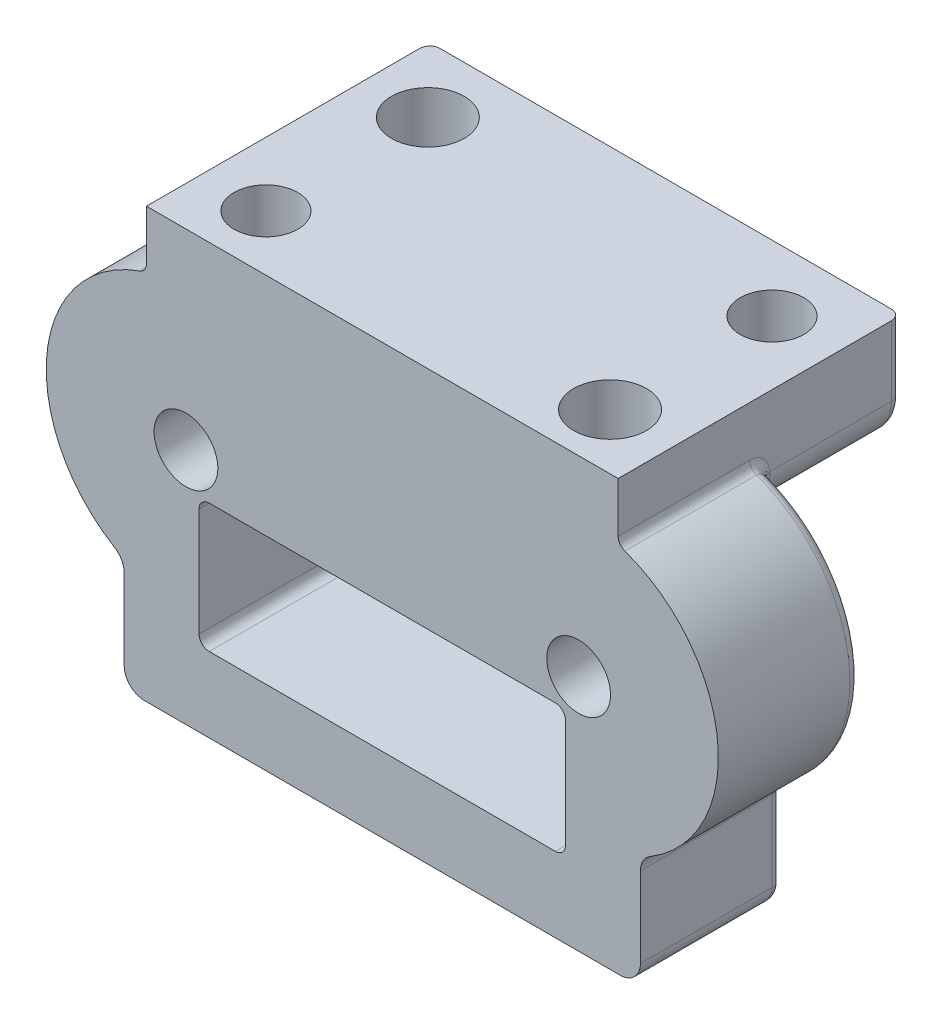
SolidWorks part; units mm, degrees
ref_plane "Спереди" through (0, 0, 0) normal (0, 0, 1) x (1, 0, 0)
ref_plane "Сверху" through (0, 0, 0) normal (0, 1, 0) x (1, 0, 0)
ref_plane "Справа" through (0, 0, 0) normal (1, 0, 0) x (0, 0, -1)
sketch "Эскиз5" plane through (0, 0, 0) normal (0, 0, 1) x (1, 0, 0)
  line L0 (7.65, 0) -> (-7.65, 0) construction
  line L1 (-7.65, 0) -> (-7.65, -1.75) construction
  line L2 (-9.7, -2.55) -> (-8.45, -2.55) construction
  line L3 (-9.7, -8.35) -> (-8.45, -8.35) construction
  line L4 (-8.75, -8.15) -> (-8.75, -9.25) construction
  line L5 (-8.75, -9.25) -> (-8.75, -13.2) construction
  line L6 (8.75, -13.2) -> (-8.75, -13.2) construction
  line L7 (8.75, -9.25) -> (8.75, -8.15) construction
  line L8 (8.75, -9.25) -> (8.75, -13.2) construction
  line L9 (9.7, -8.35) -> (8.45, -8.35) construction
  line L10 (9.7, -2.55) -> (8.45, -2.55) construction
  line L11 (7.65, -1.75) -> (7.65, 0) construction
  line L12 (7.65, 0) -> (-7.65, 0) construction
  line L13 (-7.65, 0) -> (-7.65, -1.75) construction
  line L14 (-9.7, -2.55) -> (-8.45, -2.55) construction
  line L15 (-9.7, -8.35) -> (-8.45, -8.35) construction
  line L16 (-8.75, -8.15) -> (-8.75, -9.25) construction
  line L17 (-8.75, -9.25) -> (-8.75, -13.2) construction
  line L18 (8.75, -13.2) -> (-8.75, -13.2) construction
  line L19 (8.75, -9.25) -> (8.75, -8.15) construction
  line L20 (8.75, -9.25) -> (8.75, -13.2) construction
  line L21 (9.7, -8.35) -> (8.45, -8.35) construction
  line L22 (9.7, -2.55) -> (8.45, -2.55) construction
  line L23 (7.65, -1.75) -> (7.65, 0) construction
  line L25 (11.65, 1.1687) -> (11.65, 1.1687)
  line L26 (11.65, 1.1687) -> (11.65, 4)
  line L27 (11.65, 4) -> (-11.65, 4)
  line L28 (-11.65, 4) -> (-11.65, 1.1687)
  line L29 (-11.65, 1.1687) -> (-11.65, 1.1687)
  line L30 (12.75, -9.25) -> (12.75, -17.2) construction
  line L31 (-12.75, -9.25) -> (-12.75, -17.2) construction
  line L32 (-12.75, -11.6393) -> (-12.75, -17.2)
  line L33 (12.75, -17.2) -> (-12.75, -17.2)
  line L34 (12.75, -11.6393) -> (12.75, -17.2)
  line L36 (12.75, -9.25) -> (12.75, -8.15) construction
  line L37 (9.7, -12.35) -> (8.45, -12.35) construction
  line L38 (-9.7, -12.35) -> (-8.45, -12.35) construction
  line L39 (-12.75, -8.15) -> (-12.75, -9.25) construction
  arc A0 (-8.45, -2.55) -> (-7.65, -1.75) centre (-8.45, -1.75) ccw construction
  arc A1 (-9.7, -2.55) -> (-9.7, -8.35) centre (-9.7, -5.45) ccw construction
  arc A2 (9.7, -8.35) -> (9.7, -2.55) centre (9.7, -5.45) ccw construction
  arc A3 (7.65, -1.75) -> (8.45, -2.55) centre (8.45, -1.75) ccw construction
  arc A4 (-8.45, -2.55) -> (-7.65, -1.75) centre (-8.45, -1.75) ccw construction
  arc A5 (-9.7, -2.55) -> (-9.7, -8.35) centre (-9.7, -5.45) ccw construction
  arc A6 (9.7, -8.35) -> (9.7, -2.55) centre (9.7, -5.45) ccw construction
  arc A7 (7.65, -1.75) -> (8.45, -2.55) centre (8.45, -1.75) ccw construction
  arc A8 (12.75, -11.6393) -> (11.65, 1.1687) centre (9.7, -5.45) ccw
  arc A9 (11.65, 1.1687) -> (11.65, 1.1687) centre (11.65, 1.1687) ccw
  arc A10 (-11.65, 1.1687) -> (-11.65, 1.1687) centre (-11.65, 1.1687) ccw
  arc A11 (-11.65, 1.1687) -> (-12.75, -11.6393) centre (-9.7, -5.45) ccw
  arc A13 (9.7, -12.35) -> (11.65, 1.1687) centre (9.7, -5.45) ccw construction
  arc A14 (-11.65, 1.1687) -> (-9.7, -12.35) centre (-9.7, -5.45) ccw construction
  dimension "D1" = 4
extrude "Бобышка-Вытянуть2" add sketch "Эскиз5" against normal up to surface (7 mm away)
hole_wizard "Сверло под метчик  спиральное M31" positions "Эскиз6" profile "Эскиз8" hole size "M3x0.5" standard "DIN" end condition through all
sketch "Эскиз6" plane through (0, 0, -7) normal (0, 0, -1) x (-1, 0, 0)
  point P0 (-9.7, -5.45)
  point P3 (9.7, -5.45)
sketch "Эскиз8" plane through (9.7, -5.45, -7) normal (1, 0, 0) x (0, 1, 0)
  line L0 (0, 0) -> (0, 7)
  line L1 (0, 7) -> (1.575, 7)
  line L2 (1.575, 7) -> (1.575, 0)
  line L5 (1.575, 0) -> (0, 0)
  line L11 (0, -6.35) -> (0, 107.95) construction
  dimension "Диаметр сквозного отверстия" = 3.15
  dimension "Глубина сквозного отверстия" = 7
sketch "Эскиз9" plane through (0, 0, -7) normal (0, 0, -1) x (-1, 0, 0)
  line L0 (8.75, -9.25) -> (8.75, -13.2) construction
  line L1 (-8.75, -9.25) -> (-8.75, -13.2) construction
  line L2 (-8.75, -13.2) -> (8.75, -13.2) construction
  line L3 (5, -7.45) -> (-5, -7.45) construction
  line L4 (8.75, -9.25) -> (8.75, -13.2) construction
  line L5 (-8.75, -9.25) -> (-8.75, -13.2) construction
  line L6 (-8.75, -13.2) -> (8.75, -13.2) construction
  line L7 (5, -7.45) -> (-5, -7.45) construction
  line L8 (-8.75, -9.25) -> (-8.75, -7.45) construction
  line L10 (-5, -7.45) -> (-8.75, -7.45) construction
  line L12 (5, -7.45) -> (8.75, -7.45) construction
  line L13 (8.75, -9.25) -> (8.75, -7.45) construction
  line L14 (-8.75, -7.45) -> (8.75, -13.2) construction
  line L15 (-8.75, -13.2) -> (8.75, -7.45) construction
  line L17 (-9.05, -13.5) -> (9.05, -13.5)
  line L18 (-9.05, -13.5) -> (-9.05, -7.15)
  line L19 (-9.05, -7.15) -> (9.05, -7.15)
  line L20 (9.05, -13.5) -> (9.05, -7.15)
  line L21 (-9.05, -13.5) -> (9.05, -7.15) construction
  line L22 (-9.05, -7.15) -> (9.05, -13.5) construction
  point P8 (0, -10.325)
  dimension "D1" = 0.3
  dimension "D2" = 0.3
extrude "Вырез-Вытянуть1" cut sketch "Эскиз9" against normal through all
fillet "Скругление3" radius 0.5 4 edges at (-9.05, -7.15, -3.5) (9.05, -7.15, -3.5) (-9.05, -13.5, -3.5) (9.05, -13.5, -3.5)
sketch "Эскиз10" plane through (0, 0, -7) normal (0, 0, -1) x (-1, 0, 0)
  line L0 (11.65, 4) -> (11.65, 1.1687) construction
  line L1 (-11.65, 1.1687) -> (-11.65, 4) construction
  line L2 (-11.65, 4) -> (11.65, 4) construction
  line L3 (11.65, 4) -> (11.65, 1.1687) construction
  line L4 (-11.65, 1.1687) -> (-11.65, 4) construction
  line L5 (-11.65, 4) -> (11.65, 4) construction
  line L7 (-11.65, -7.15) -> (11.65, -7.15)
  line L8 (-11.65, -7.15) -> (-11.65, 4)
  line L9 (-11.65, 4) -> (11.65, 4)
  line L10 (11.65, -7.15) -> (11.65, 4)
  line L11 (-11.65, -7.15) -> (11.65, 4) construction
  line L12 (-11.65, 4) -> (11.65, -7.15) construction
  line L13 (8.55, -7.15) -> (-8.55, -7.15) construction
  line L14 (8.55, -7.15) -> (-8.55, -7.15) construction
  point P6 (0, -1.575)
extrude "Бобышка-Вытянуть3" add sketch "Эскиз10" along normal blind 7
sketch "Эскиз14" plane through (0, 0, -14) normal (0, 0, -1) x (-1, 0, 0)
  circle A0 centre (-9.7, -5.45) radius 4
  circle A1 centre (9.7, -5.45) radius 4
  dimension "D1" = 8
extrude "Вырез-Вытянуть4" cut sketch "Эскиз14" against normal up to surface (7 mm away) up to face at (0, -9.4681, -7)
fillet "Скругление9" radius 2 4 edges at (11.65, -1.9575, -10.5) (6.0792, -7.15, -10.5) (-6.0792, -7.15, -10.5) (-11.65, -1.9575, -10.5)
fillet "Скругление10" radius 0.5 22 edges at (11.65, 1.1687, -3.5) (-11.65, 1.1687, -3.5) (11.0701, -0.8585, -7) (6.9311, -2.5632, -7) (-5.0859, -6.5991, -7) (-6.9311, -2.5632, -7) (11.65, 2.2749, -14) (11.0701, -0.8585, -14) (6.9311, -2.5632, -14) (5.0859, -6.5991, -14) (0, -7.15, -14) (-5.0859, -6.5991, -14) (-6.9311, -2.5632, -14) (-11.0701, -0.8585, -14) (12.75, -14.4197, -7) (0, -17.2, -7) (-12.75, -14.4197, -7) (-16.5747, -4.8596, -7) (16.5747, -4.8596, -7) (5.0859, -6.5991, -7) (-11.0701, -0.8585, -7) (-11.65, 2.2749, -14)
fillet "Скругление11" radius 1 8 edges at (-12.6663, -11.587, -6.777) (-12.6036, -17.0536, -6.8536) (12.6036, -17.0536, -6.8536) (12.6663, -11.587, -6.777) (-12.75, -11.6393, -3.25) (-12.75, -17.2, -3.25) (12.75, -17.2, -3.25) (12.75, -11.6393, -3.25)
sketch "Эскиз15" plane through (0, 4, 0) normal (0, 1, 0) x (1, 0, 0)
  line L0 (11.65, 13.5) -> (11.65, 0) construction
  line L1 (11.65, 0) -> (-11.65, 0) construction
  line L2 (-11.65, 13.5) -> (-11.65, 0) construction
  line L3 (-11.15, 14) -> (11.15, 14) construction
  line L4 (11.65, 13.5) -> (11.65, 0) construction
  line L5 (11.65, 0) -> (-11.65, 0) construction
  line L6 (-11.65, 13.5) -> (-11.65, 0) construction
  line L7 (-11.15, 14) -> (11.15, 14) construction
  line L8 (-11.65, 6.75) -> (11.65, 6.75) construction
  line L9 (0, 14) -> (0, 0) construction
  line L11 (-8.5, 2.75) -> (8.5, 2.75) construction
  line L12 (-8.5, 2.75) -> (-8.5, 10.75) construction
  line L13 (-8.5, 10.75) -> (8.5, 10.75) construction
  line L14 (8.5, 2.75) -> (8.5, 10.75) construction
  line L15 (-8.5, 2.75) -> (8.5, 10.75) construction
  line L16 (-8.5, 10.75) -> (8.5, 2.75) construction
  point P10 (0, 6.75)
  dimension "D1" = 17
  dimension "D2" = 8
hole_wizard "Сверло под метчик  спиральное M30" positions "Эскиз16" profile "Эскиз17" hole size "M3x0.5" standard "DIN"
sketch "Эскиз16" plane through (0, 4, 0) normal (0, 1, 0) x (1, 0, 0)
  point P0 (-8.5, 10.75)
  point P3 (8.5, 2.75)
  point P6 (-8.5, 2.75)
  point P8 (8.5, 10.75)
sketch "Эскиз17" plane through (-8.5, 4, -10.75) normal (1, 0, 0) x (0, 0, 1)
  line L0 (0, 0) -> (0, 4.9464)
  line L1 (0, 4.9464) -> (1.575, 4)
  line L2 (1.575, 4) -> (1.575, 0)
  line L5 (1.575, 0) -> (0, 0)
  line L10 (0, 4.9464) -> (-1.575, 4) construction
  line L11 (0, -6.35) -> (0, 107.95) construction
  dimension "Диаметр отверстия" = 3.15
  dimension "Глубина отверстия" = 4
  dimension "Угол заточки сверла" = 118
sketch "Эскиз18" plane through (0, 4, 0) normal (0, 1, 0) x (1, 0, 0)
  circle A0 centre (8.5, 2.75) radius 1.575 construction
  circle A1 centre (-8.5, 10.75) radius 1.575 construction
  circle A6 centre (8.5, 2.75) radius 1.575 construction
  circle A7 centre (-8.5, 10.75) radius 1.575 construction
  circle A8 centre (-8.5, 10.75) radius 1.8
  circle A9 centre (8.5, 2.75) radius 1.8
  dimension "D1" = 3.6
extrude "Вырез-Вытянуть5" cut sketch "Эскиз18" against normal blind 3
